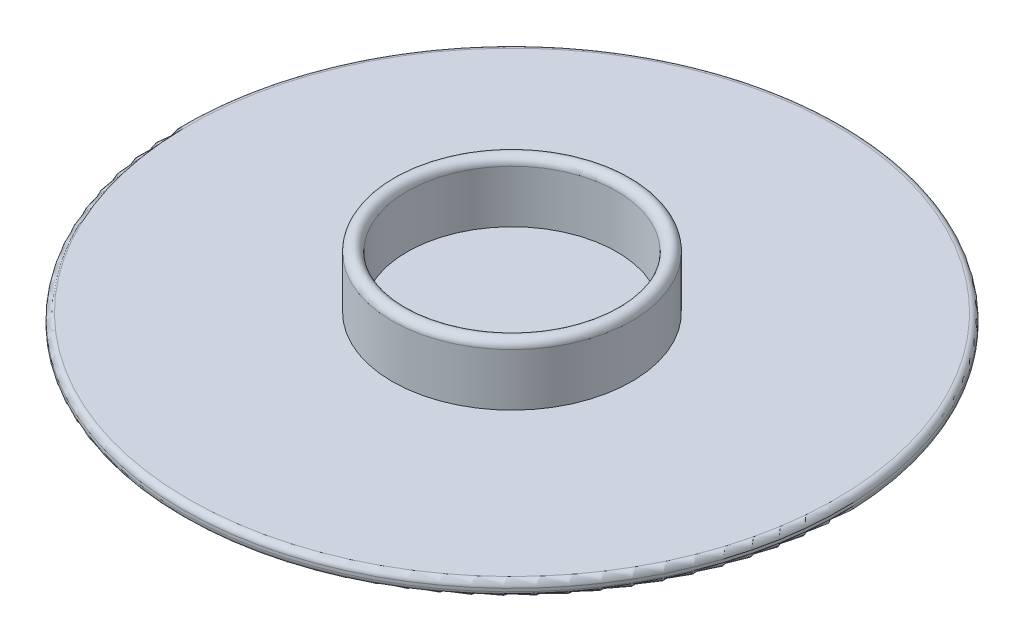
SolidWorks part; units mm, degrees
ref_plane "前视基准面" through (0, 0, 0) normal (0, 0, 1) x (1, 0, 0)
ref_plane "上视基准面" through (0, 0, 0) normal (0, 1, 0) x (1, 0, 0)
ref_plane "右视基准面" through (0, 0, 0) normal (1, 0, 0) x (0, 0, -1)
sketch "草图1" plane through (0, 0, 0) normal (0, 1, 0) x (1, 0, 0)
  circle A0 centre (0, 0) radius 11
  dimension "D1" = 22
extrude "凸台-拉伸1" add sketch "草图1" along normal blind 0.5
sketch "草图2" plane through (0, 0.5, 0) normal (0, 1, 0) x (1, 0, 0)
  circle A0 centre (0, 0) radius 4
  circle A1 centre (0, 0) radius 3.5
  dimension "D1" = 8
  dimension "D2" = 0.5
extrude "凸台-拉伸2" add sketch "草图2" along normal blind 2
fillet "圆角1" 2 edges at (0, 2.5, 4) (0, 2.5, 3.5) type full round first side face at (0, 2.5, 4) second side face at (0, 2.5, 3.5) middle face at (0, 2.5, 4)
sketch "草图3" plane through (0, 0, 0) normal (1, 0, 0) x (0, 0, -1)
  line L0 (0, -0.1067) -> (0, 3.8988) construction
  line L1 (0, 0) -> (8, 0) construction
  line L2 (-11, 0) -> (11, 0) construction
  line L3 (0, 0.3) -> (1.1875, 0.3) construction
  line L4 (0, 0) -> (8, 0)
  line L5 (0, 0) -> (0, 0.3)
  arc A0 (8, 0) -> (0, 0.3) centre (0, -106.5167) ccw
  dimension "D1" = 8
  dimension "D2" = 0.3
revolve "切除-旋转2" cut sketch "草图3" angle 360 about L5
fillet "圆角2" radius 0.2 2 edges at (0, 0, 11) (0, 0.5, 11)
equation "\"、\"=2"
